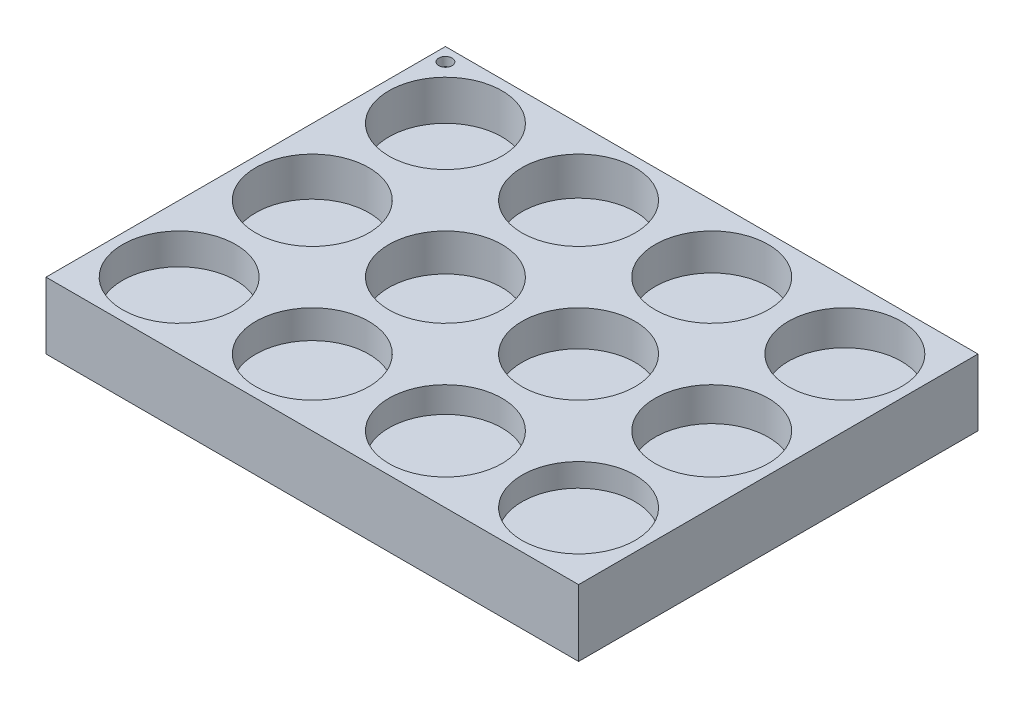
SolidWorks part; units mm, degrees
ref_plane "Front Plane" through (0, 0, 0) normal (0, 0, 1) x (1, 0, 0)
ref_plane "Top Plane" through (0, 0, 0) normal (0, 1, 0) x (1, 0, 0)
ref_plane "Right Plane" through (0, 0, 0) normal (1, 0, 0) x (0, 0, -1)
sketch "Sketch1" plane through (0, 0, 0) normal (0, 1, 0) x (1, 0, 0)
  line L0 (-45, 30) -> (45, 30) construction
  line L1 (60, -45) -> (-60, -45)
  line L2 (60, -45) -> (60, 45)
  line L3 (60, 45) -> (-60, 45)
  line L4 (-60, -45) -> (-60, 45)
  line L5 (60, -45) -> (-60, 45) construction
  line L6 (60, 45) -> (-60, -45) construction
  line L8 (-15, 45) -> (15, 45) construction
  line L9 (-15, 45) -> (-15, 0) construction
  line L10 (-15, 0) -> (15, 0) construction
  line L11 (15, 45) -> (15, 0) construction
  circle A0 centre (-45, 30) radius 6.65
  circle A1 centre (-15, 30) radius 6.65
  circle A2 centre (15, 30) radius 6.65
  circle A3 centre (45, 30) radius 6.65
  circle A4 centre (-45, 0) radius 6.65
  circle A5 centre (-15, 0) radius 6.65
  circle A6 centre (15, 0) radius 6.65
  circle A7 centre (45, 0) radius 6.65
  circle A8 centre (-45, -30) radius 6.65
  circle A9 centre (-15, -30) radius 6.65
  circle A10 centre (15, -30) radius 6.65
  circle A11 centre (45, -30) radius 6.65
  point P0 (0, 0)
  point P14 (0, 30)
  point P15 (0, 0)
  dimension "D3" = 13.3
  dimension "D1" = 120
  dimension "D2" = 90
  dimension "D4" = 15
  dimension "D5" = 15
  dimension "D6" = 30
  dimension "D8" = 30
  dimension "D7" = 3
extrude "Boss-Extrude1" add sketch "Sketch1" along normal blind 5
sketch "Sketch3" plane through (0, 5, 0) normal (0, 1, 0) x (1, 0, 0)
  line L1 (-60, 45) -> (60, 45)
  line L2 (-60, 45) -> (-60, -45)
  line L3 (-60, -45) -> (60, -45)
  line L4 (60, 45) -> (60, -45)
extrude "Boss-Extrude6" add sketch "Sketch3" along normal blind 10
sketch "Sketch2" plane through (0, 15, 0) normal (0, 1, 0) x (1, 0, 0)
  line L1 (-60, 45) -> (-30, 45) construction
  line L2 (-60, 45) -> (-60, 15) construction
  line L3 (-60, 15) -> (-30, 15) construction
  line L4 (-30, 45) -> (-30, 15) construction
  line L5 (-60, 15) -> (-30, 15) construction
  line L6 (-60, 15) -> (-60, -15) construction
  line L7 (-60, -15) -> (-30, -15) construction
  line L8 (-30, 15) -> (-30, -15) construction
  line L9 (-60, -15) -> (-30, -15) construction
  line L10 (-60, -15) -> (-60, -45) construction
  line L11 (-60, -45) -> (-30, -45) construction
  line L12 (-30, -15) -> (-30, -45) construction
  line L14 (-30, 45) -> (0, 45) construction
  line L15 (-30, 45) -> (-30, 15) construction
  line L16 (-30, 15) -> (0, 15) construction
  line L17 (0, 45) -> (0, 15) construction
  line L18 (-30, 15) -> (0, 15) construction
  line L19 (-30, 15) -> (-30, -15) construction
  line L20 (-30, -15) -> (0, -15) construction
  line L21 (0, 15) -> (0, -15) construction
  line L22 (-30, -15) -> (0, -15) construction
  line L23 (-30, -15) -> (-30, -45) construction
  line L24 (-30, -45) -> (0, -45) construction
  line L25 (0, -15) -> (0, -45) construction
  line L26 (0, 45) -> (30, 45) construction
  line L27 (0, 45) -> (0, 15) construction
  line L28 (0, 15) -> (30, 15) construction
  line L29 (30, 45) -> (30, 15) construction
  line L30 (0, 15) -> (30, 15) construction
  line L31 (0, 15) -> (0, -15) construction
  line L32 (0, -15) -> (30, -15) construction
  line L33 (30, 15) -> (30, -15) construction
  line L34 (0, -15) -> (30, -15) construction
  line L35 (0, -15) -> (0, -45) construction
  line L36 (0, -45) -> (30, -45) construction
  line L37 (30, -15) -> (30, -45) construction
  line L38 (30, 45) -> (60, 45) construction
  line L39 (30, 45) -> (30, 15) construction
  line L40 (30, 15) -> (60, 15) construction
  line L41 (60, 45) -> (60, 15) construction
  line L43 (30, 15) -> (60, 15) construction
  line L44 (30, 15) -> (30, -15) construction
  line L45 (30, -15) -> (60, -15) construction
  line L46 (60, 15) -> (60, -15) construction
  line L47 (30, -15) -> (60, -15) construction
  line L48 (30, -15) -> (30, -45) construction
  line L49 (30, -45) -> (60, -45) construction
  line L50 (60, -15) -> (60, -45) construction
  circle A0 centre (-45, 30) radius 12.75
  circle A1 centre (-15, 30) radius 12.75
  circle A2 centre (15, 30) radius 12.75
  circle A3 centre (45, 30) radius 12.75
  circle A4 centre (-45, 0) radius 12.75
  circle A5 centre (-15, 0) radius 12.75
  circle A6 centre (15, 0) radius 12.75
  circle A7 centre (45, 0) radius 12.75
  circle A8 centre (-45, -30) radius 12.75
  circle A9 centre (-15, -30) radius 12.75
  circle A10 centre (15, -30) radius 12.75
  circle A11 centre (45, -30) radius 12.75
  point P33 (-45, 45)
  point P35 (-60, 30)
  point P38 (-15, 15)
  point P40 (15, 15)
  point P42 (45, 15)
  dimension "D1" = 25.5
  dimension "D3" = 30
  dimension "D2" = 3
extrude "Cut-Extrude1" cut sketch "Sketch2" against normal offset from surface (9 mm away) 1 contours A0 region at (-45, 15, -30) up to face at (-45, 5, -23.35)
extrude "Cut-Extrude2" cut sketch "Sketch2<8>" against normal offset from surface (8.8 mm away) 1.2 contours A4 region at (-45, 15, 0) up to face at (-45, 5, 6.65)
sketch "Sketch2<8>" plane through (0, 15, 0) normal (0, 1, 0) x (1, 0, 0) same geometry as "Sketch2"
extrude "Cut-Extrude3" cut sketch "Sketch2<9>" against normal offset from surface (7 mm away) 3 contours A8 region at (-45, 15, 30) up to face at (-45, 5, 36.65)
sketch "Sketch2<9>" plane through (0, 15, 0) normal (0, 1, 0) x (1, 0, 0) same geometry as "Sketch2"
extrude "Cut-Extrude4" cut sketch "Sketch2<10>" against normal offset from surface (8.6 mm away) 1.4 contours A1 region at (-15, 15, -30) up to face at (-15, 5, -23.35)
sketch "Sketch2<10>" plane through (0, 15, 0) normal (0, 1, 0) x (1, 0, 0) same geometry as "Sketch2"
extrude "Cut-Extrude5" cut sketch "Sketch2<11>" against normal offset from surface (8.4 mm away) 1.6 contours A5 region at (-15, 15, 0) up to face at (-15, 5, 6.65)
sketch "Sketch2<11>" plane through (0, 15, 0) normal (0, 1, 0) x (1, 0, 0) same geometry as "Sketch2"
extrude "Cut-Extrude6" cut sketch "Sketch2<12>" against normal offset from surface (6.4 mm away) 3.6 contours A9 region at (-15, 15, 30) up to face at (-15, 5, 36.65)
sketch "Sketch2<12>" plane through (0, 15, 0) normal (0, 1, 0) x (1, 0, 0) same geometry as "Sketch2"
extrude "Cut-Extrude7" cut sketch "Sketch2<13>" against normal offset from surface (8.2 mm away) 1.8 contours A2 region at (15, 15, -30) up to face at (15, 5, -23.35)
sketch "Sketch2<13>" plane through (0, 15, 0) normal (0, 1, 0) x (1, 0, 0) same geometry as "Sketch2"
extrude "Cut-Extrude8" cut sketch "Sketch2<14>" against normal offset from surface (8 mm away) 2 contours A6 region at (15, 15, 0) up to face at (15, 5, 6.65)
sketch "Sketch2<14>" plane through (0, 15, 0) normal (0, 1, 0) x (1, 0, 0) same geometry as "Sketch2"
extrude "Cut-Extrude9" cut sketch "Sketch2<15>" against normal offset from surface (5.8 mm away) 4.2 contours A10 region at (15, 15, 30) up to face at (15, 5, 36.65)
sketch "Sketch2<15>" plane through (0, 15, 0) normal (0, 1, 0) x (1, 0, 0) same geometry as "Sketch2"
extrude "Cut-Extrude10" cut sketch "Sketch2<16>" against normal offset from surface (7.8 mm away) 2.2 contours A3 region at (45, 15, -30) up to face at (45, 5, -23.35)
sketch "Sketch2<16>" plane through (0, 15, 0) normal (0, 1, 0) x (1, 0, 0) same geometry as "Sketch2"
extrude "Cut-Extrude11" cut sketch "Sketch2<17>" against normal offset from surface (7.6 mm away) 2.4 contours A7 region at (45, 15, 0) up to face at (45, 5, 6.65)
sketch "Sketch2<17>" plane through (0, 15, 0) normal (0, 1, 0) x (1, 0, 0) same geometry as "Sketch2"
extrude "Cut-Extrude12" cut sketch "Sketch2<18>" against normal offset from surface (5.2 mm away) 4.8 contours A11 region at (45, 15, 30) up to face at (45, 5, 36.65)
sketch "Sketch2<18>" plane through (0, 15, 0) normal (0, 1, 0) x (1, 0, 0) same geometry as "Sketch2"
sketch "Sketch4" plane through (0, 15, 0) normal (0, 1, 0) x (1, 0, 0)
  line L0 (-60, 45) -> (-54.0156, 39.0156) construction
  line L1 (60, 45) -> (-60, 45) construction
  circle A0 centre (-57.0078, 42.0078) radius 1.5
  circle A1 centre (-45, 30) radius 12.75 construction
  point P10 (-57.0078, 42.0078)
  dimension "D2" = 3
  dimension "D1" = 45
extrude "Cut-Extrude13" cut sketch "Sketch4" against normal blind 2
sketch "Sketch5" plane through (0, 15, 0) normal (0, 1, 0) x (1, 0, 0)
  line L0 (-60, 45) -> (-60, -45) construction
  line L1 (-60, -15) -> (60, -15)
  line L2 (-60, -15) -> (-60, -45)
  line L3 (-60, -45) -> (60, -45)
  line L4 (60, -15) -> (60, -45)
  dimension "D1" = 30
extrude "Cut-Extrude14" [suppressed] cut sketch "Sketch5" against normal through all
